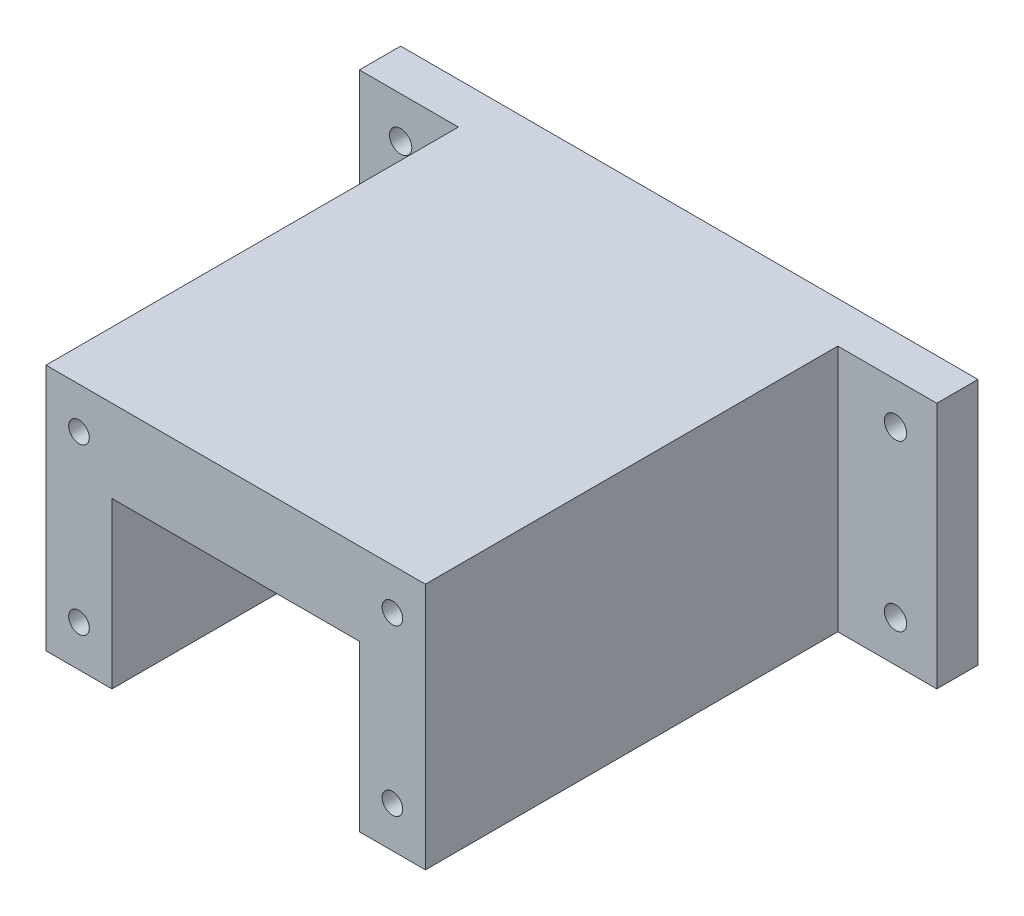
SolidWorks part; units mm, degrees
ref_plane "前基準面" through (0, 0, 0) normal (0, 0, 1) x (1, 0, 0)
ref_plane "上基準面" through (0, 0, 0) normal (0, 1, 0) x (1, 0, 0)
ref_plane "右基準面" through (0, 0, 0) normal (1, 0, 0) x (0, 0, -1)
ref_axis "基準軸1" through (0, -55, 0) along (0, 1, 0)
ref_axis "基準軸2" through (-88.99, 0, 0) along (1, 0, 0)
ref_axis "基準軸3" through (0, 0, 55) along (0, 0, -1)
sketch "草圖1" plane through (0, 0, 0) normal (0, 0, 1) x (1, 0, 0)
  line L0 (20, 0) -> (20, 10)
  line L1 (0, 0) -> (20, 0)
  line L2 (0, 0) -> (0, 30)
  line L3 (0, 30) -> (70, 30)
  line L4 (70, 0) -> (70, 30)
  line L5 (20, 10) -> (50, 10)
  line L6 (50, 10) -> (50, 0)
  line L7 (50, 0) -> (70, 0)
  circle A0 centre (5, 25) radius 1.35
  circle A1 centre (5, 5) radius 1.35
  circle A2 centre (65, 25) radius 1.35
  circle A3 centre (65, 5) radius 1.35
  dimension "D6" = 2.7
  dimension "D7" = 2.7
  dimension "D8" = 2.7
  dimension "D9" = 2.7
  dimension "D1" = 70
  dimension "D2" = 30
  dimension "D3" = 30
  dimension "D4" = 10
  dimension "D5" = 20
  dimension "D10" = 5
  dimension "D11" = 5
  dimension "D12" = 5
  dimension "D13" = 5
  dimension "D14" = 5
  dimension "D15" = 5
  dimension "D16" = 5
  dimension "D17" = 5
extrude "填料-伸長1" add sketch "草圖1" along normal blind 5
sketch "草圖2" plane through (0, 0, 5) normal (0, 0, 1) x (1, 0, 0)
  line L0 (20, 20) -> (20, 0)
  line L1 (2.75, 0) -> (-2.75, 0) construction
  line L2 (20, 0) -> (20, 10) construction
  line L3 (20, 0) -> (12, 0)
  line L4 (12, 0) -> (12, 30)
  line L5 (70, 30) -> (0, 30) construction
  line L6 (12, 30) -> (58, 30)
  line L7 (58, 30) -> (58, 0)
  line L8 (58, 0) -> (50, 0)
  line L9 (50, 0) -> (50, 20)
  line L10 (50, 20) -> (20, 20)
  point P17 (50, 0)
  point P18 (50, 0)
  dimension "D1" = 8
  dimension "D2" = 8
  dimension "D3" = 46
  dimension "D4" = 20
extrude "填料-伸長2" add sketch "草圖2" along normal blind 50
sketch "草圖3" plane through (0, 0, 55) normal (0, 0, 1) x (1, 0, 0)
  line L0 (58, 30) -> (12, 30) construction
  line L1 (12, 30) -> (12, 0) construction
  circle A0 centre (16, 25) radius 1.25
  point P2 (0, 0)
  dimension "D1" = 2.5
  dimension "D2" = 5
  dimension "D3" = 4
extrude "除料-伸長1" cut sketch "草圖3" against normal blind 10
ref_plane "平面1" through (35, 0, 0) normal (1, 0, 0) x (0, 0, -1)
mirror "鏡射1" about plane through (35, 0, 0) normal (1, 0, 0) of "除料-伸長1"
ref_plane "平面2" through (0, 15, 0) normal (0, 1, 0) x (1, 0, 0)
mirror "鏡射2" about plane through (0, 15, 0) normal (0, 1, 0) of "鏡射1"
